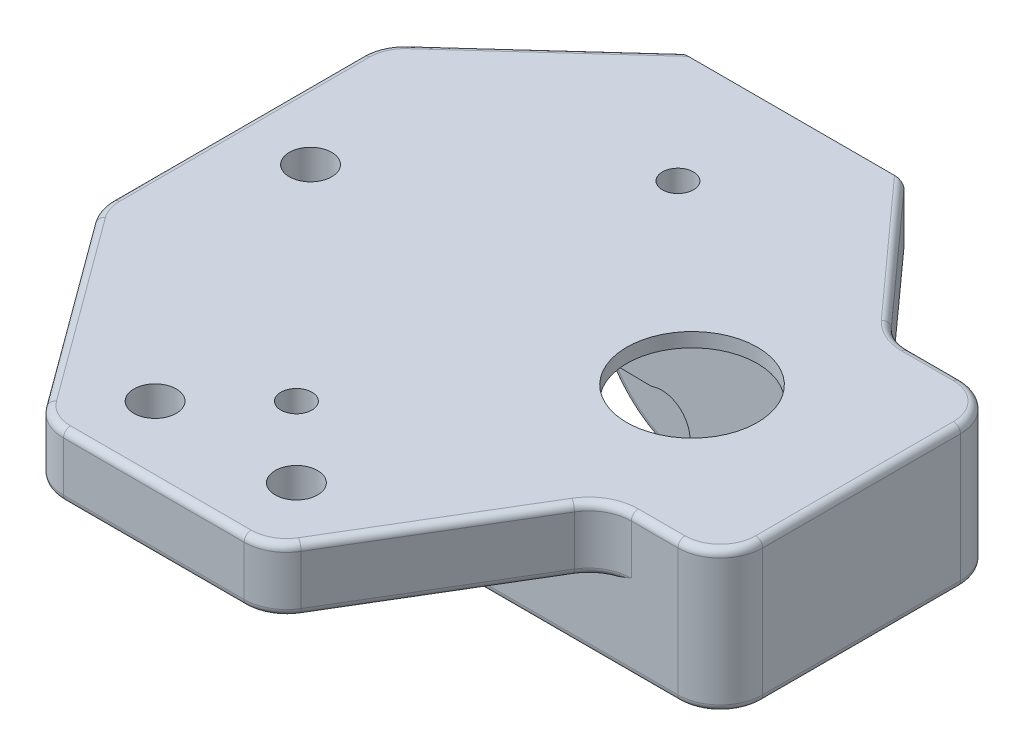
SolidWorks part; units mm, degrees
ref_plane "Front Plane" through (0, 0, 0) normal (0, 0, 1) x (1, 0, 0)
ref_plane "Top Plane" through (0, 0, 0) normal (0, 1, 0) x (1, 0, 0)
ref_plane "Right Plane" through (0, 0, 0) normal (1, 0, 0) x (0, 0, -1)
sketch "Sketch1" plane through (0, 0, 0) normal (0, 1, 0) x (1, 0, 0)
  line L0 (0, 0) -> (16, 0)
  line L1 (16, 0) -> (25, 15)
  line L2 (25, 15) -> (33, 15)
  line L3 (33, 15) -> (33, 35)
  line L4 (33, 35) -> (25, 35)
  line L5 (25, 35) -> (16, 45)
  line L6 (16, 45) -> (0, 45)
  line L7 (0, 45) -> (-11, 35)
  line L8 (-11, 35) -> (-11, 15)
  line L9 (-11, 15) -> (0, 0)
  dimension "D1" = 44
  dimension "D2" = 10
  dimension "D3" = 20
  dimension "D4" = 8
  dimension "D5" = 8
  dimension "D6" = 16
  dimension "D7" = 16
  dimension "D8" = 20
  dimension "D9" = 15
  dimension "D10" = 10
  dimension "D11" = 17
  dimension "D12" = 17
extrude "Boss-Extrude1" add sketch "Sketch1" along normal blind 4.5
sketch "Sketch2" plane through (0, 0, 0) normal (0, -1, 0) x (-1, 0, 0)
  line L1 (-33, 15) -> (1, 15)
  line L2 (-33, 15) -> (-33, 35)
  line L3 (-33, 35) -> (1, 35)
  line L4 (1, 15) -> (1, 35)
  dimension "D1" = 20
  dimension "D2" = 34
extrude "Boss-Extrude2" add sketch "Sketch2" along normal blind 5.5
sketch "Sketch3" plane through (0, -5.5, 0) normal (0, -1, 0) x (-1, 0, 0)
  line L0 (-33, 35) -> (-33, 15) construction
  circle A0 centre (-21, 25) radius 4.6217
  dimension "D1" = 25
  dimension "D2" = 12
extrude "Cut-Extrude1" cut sketch "Sketch3" against normal blind 15.5
sketch "Sketch4" plane through (0, -5.5, 0) normal (0, -1, 0) x (1, 0, 0)
  line L1 (4.6, -18.5) -> (27, -18.5)
  line L2 (4.6, -18.5) -> (4.6, -31.1)
  line L3 (4.6, -31.1) -> (27, -31.1)
  line L4 (27, -18.5) -> (27, -31.1)
  dimension "D1" = 22.4
  dimension "D2" = 12.6
  dimension "D3" = 18.5
  dimension "D4" = 4.6
extrude "Cut-Extrude2" cut sketch "Sketch4" against normal blind 9
sketch "Sketch5" plane through (0, 0, 0) normal (0, -1, 0) x (-1, 0, 0)
  circle A0 centre (-3, 5) radius 1.5
  circle A1 centre (-13, 5) radius 1.5
  dimension "D2" = 3
  dimension "D3" = 3
  dimension "D1" = 10
  dimension "D4" = 5
  dimension "D5" = 5
  dimension "D6" = 3
extrude "Cut-Extrude3" cut sketch "Sketch5" against normal blind 9
sketch "Sketch6" plane through (0, -5.5, 0) normal (0, -1, 0) x (-1, 0, 0)
  circle A0 centre (-2, 25) radius 1
  circle A1 centre (-30, 25) radius 1
  dimension "D3" = 2
  dimension "D4" = 2
  dimension "D1" = 25
  dimension "D2" = 25
  dimension "D5" = 30
  dimension "D6" = 2
extrude "Cut-Extrude4" cut sketch "Sketch6" against normal blind 9
sketch "Sketch7" plane through (0, 0, 0) normal (0, -1, 0) x (-1, 0, 0)
  circle A0 centre (6, 25) radius 1.5
  circle A1 centre (-21, 25) radius 4.6217 construction
  dimension "D1" = 3
  dimension "D2" = 27
  dimension "D3" = 25
extrude "Cut-Extrude5" cut sketch "Sketch7" against normal blind 19
sketch "Sketch8" plane through (0, 0, 0) normal (0, -1, 0) x (-1, 0, 0)
  line L1 (0, 44) -> (-16, 44)
  line L2 (0, 44) -> (0, 39)
  line L3 (0, 39) -> (-16, 39)
  line L4 (-16, 44) -> (-16, 39)
  dimension "D1" = 5
  dimension "D2" = 16
  dimension "D3" = 39
extrude "Boss-Extrude3" add sketch "Sketch8" along normal blind 15
sketch "Sketch9" plane through (0, 0, -45) normal (0, 0, -1) x (-1, 0, 0)
  circle A1 centre (-12.75, -5) radius 0.75
  circle A2 centre (-3.25, -5) radius 0.75
  dimension "D6" = 1.5
  dimension "D7" = 1.5
  dimension "D1" = 9.5
  dimension "D2" = 3.25
extrude "Cut-Extrude6" cut sketch "Sketch9" against normal blind 6
sketch "Sketch10" plane through (0, 0, -45) normal (0, 0, -1) x (-1, 0, 0)
  circle A0 centre (-8, -5) radius 2
  dimension "D3" = 4
  dimension "D1" = 8
  dimension "D2" = 5
extrude "Cut-Extrude7" cut sketch "Sketch10" against normal blind 36
fillet "Fillet1" radius 3 10 edges at (-11, 2.25, -35) (25, 2.25, -35) (33, -0.5, -35) (33, -0.5, -15) (25, 2.25, -15) (-11, 2.25, -15) (16, 2.25, 0) (0, 2.25, 0) (-1, -2.75, -35) (-1, -2.75, -15)
fillet "Fillet2" radius 8 2 edges at (16, -15, -41.5) (0, -15, -41.5)
fillet "Fillet3" radius 2 1 edges at (8, 0, -39)
sketch "Sketch11" plane through (0, 0, -39) normal (0, 0, 1) x (1, 0, 0)
  line L0 (3.25, -3) -> (12.0414, -3.1297)
  line L1 (3.25, -7) -> (12.0414, -6.8703)
  arc A0 (12.0414, -6.8703) -> (12.0414, -3.1297) centre (12.75, -5) ccw
  arc A1 (3.25, -3) -> (3.25, -7) centre (3.25, -5) ccw
  dimension "D1" = 4
  dimension "D2" = 4
extrude "Cut-Extrude8" cut sketch "Sketch11" along normal blind 30
ref_plane "Plane1" through (8, 0, 0) normal (1, 0, 0) x (0, 0, -1)
ref_plane "Plane2" through (0, -5, 0) normal (0, 1, 0) x (1, 0, 0)
ref_axis "Axis1" through (8, -5, -47.25) along (0, 0, 1)
ref_axis "Axis2" through (3, 4.5, -5) along (0, -1, 0)
ref_axis "Axis3" through (13, 4.5, -5) along (0, -1, 0)
ref_axis "Axis4" through (-6, 4.5, -25) along (0, -1, 0)
ref_plane "Plane3" through (21, 0, 0) normal (1, 0, 0) x (0, 0, -1)
ref_plane "Plane4" through (0, 0, -25) normal (0, 0, 1) x (1, 0, 0)
ref_axis "Axis5" through (21, -15.975, -25) along (0, 1, 0)
sketch "Sketch12" plane through (0, 0, 0) normal (0, -1, 0) x (-1, 0, 0)
  line L0 (-8, 10.725) -> (-8, -10.725) construction
  circle A0 centre (-8, 37) radius 1.1
  circle A2 centre (-8, 10) radius 1.1
  dimension "D1" = 2.2
  dimension "D3" = 27
  dimension "D4" = 2.2
  dimension "D2" = 8
  dimension "D5" = 37
extrude "Cut-Extrude9" cut sketch "Sketch12" against normal blind 10 and the other way blind 10
fillet "Fillet4" radius 0.5 43 edges at (-5.009, 4.5, -40.4464) (-10.7435, 4.5, -34.8866) (-11, 4.5, -24.8275) (-10.8511, 4.5, -15.0487) (-5.6591, 4.5, -7.717) (0.1642, 4.5, -0.324) (7.9108, 4.5, 0) (15.7795, 4.5, -0.3894) (20.5, 4.5, -7.5) (25.2205, 4.5, -14.6106) (28.3493, 4.5, -15) (32.1213, 4.5, -15.8787) (33, 4.5, -25) (32.1213, 4.5, -34.1213) (28.168, 4.5, -35) (25.1156, 4.5, -35.2595) (20.0531, 4.5, -40.4966) (-5.009, 0, -40.4464) (-10.7435, 0, -34.8866) (-11, 0, -24.8275) (-10.8511, 0, -15.0487) (25.2205, 0, -14.6106) (20.5, 0, -7.5) (15.7795, 0, -0.3894) (7.9108, 0, 0) (0.1642, 0, -0.324) (-5.6591, 0, -7.717) (0, -0.5858, -38.4142) (0, -4.5, -39) (2.3431, -12.6569, -39) (16, -0.5858, -38.4142) (16, -4.5, -39) (-0.3515, -5.5, -16.1371) (-0.3515, -5.5, -33.8629) (22.3432, -5.5, -35) (32.1213, -5.5, -34.1213) (33, -5.5, -25) (32.1213, -5.5, -15.8787) (13.6569, -12.6569, -39) (-1, -5.5, -25) (22.3432, -5.5, -15) (25.1156, 0, -35.2595) (20.0531, 0, -40.4966)
sketch "Sketch13" plane through (0, 0, 0) normal (0, -1, 0) x (-1, 0, 0)
  circle A0 centre (-8, 37) radius 2
  dimension "D1" = 4
extrude "Cut-Extrude10" cut sketch "Sketch13" along normal blind 10
